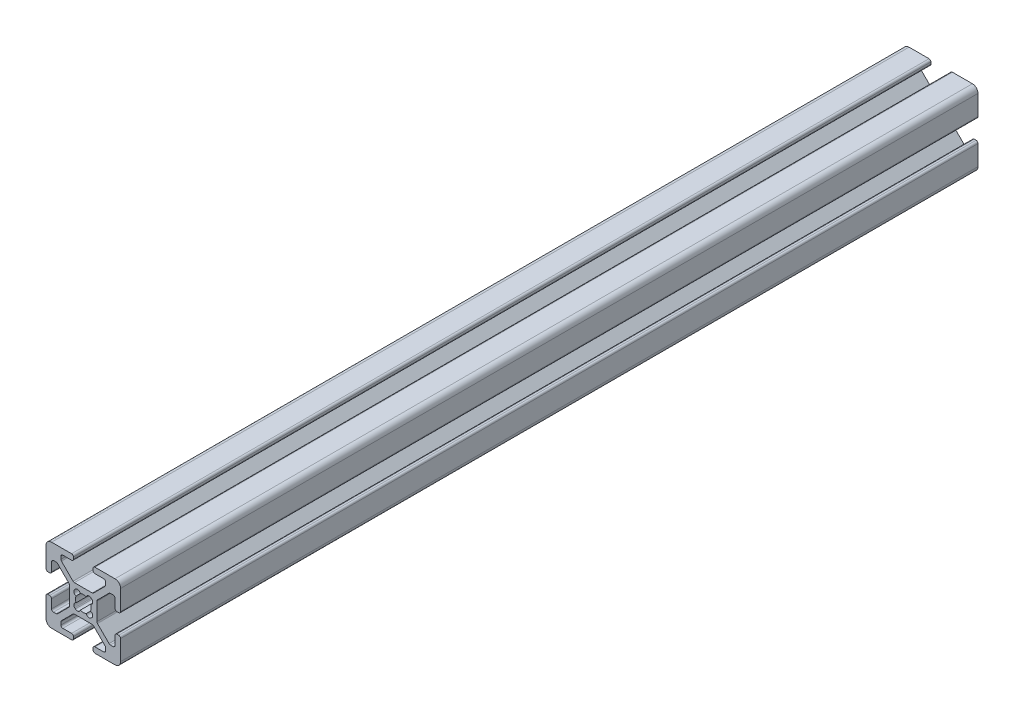
SolidWorks part; units mm, degrees
ref_plane "Front Plane" through (0, 0, 0) normal (0, 0, 1) x (1, 0, 0)
ref_plane "Top Plane" through (0, 0, 0) normal (0, 1, 0) x (1, 0, 0)
ref_plane "Right Plane" through (0, 0, 0) normal (1, 0, 0) x (0, 0, -1)
sketch "Sketch1" plane through (0, 0, 0) normal (0, 0, 1) x (1, 0, 0)
  line B0 (10, 3.138) -> (10, 8.5)
  line B1 (8.5, 10) -> (3.138, 10)
  line B2 (2.63, 9.492) -> (2.63, 9.008)
  line B3 (3.138, 8.5) -> (5.487, 8.5)
  line B4 (5.995, 7.992) -> (5.995, 7.2661)
  line B5 (5.8462, 6.9069) -> (2.7431, 3.8038)
  line B6 (2.3839, 3.655) -> (-2.3839, 3.655)
  line B7 (-2.7431, 3.8038) -> (-5.8462, 6.9069)
  line B8 (-5.995, 7.2661) -> (-5.995, 7.992)
  line B9 (-5.487, 8.5) -> (-3.138, 8.5)
  line B10 (-2.63, 9.008) -> (-2.63, 9.492)
  line B11 (-3.138, 10) -> (-8.5, 10)
  line B12 (-10, 8.5) -> (-10, 3.138)
  line B13 (-9.492, 2.63) -> (-9.008, 2.63)
  line B14 (-8.5, 3.138) -> (-8.5, 5.487)
  line B15 (-7.992, 5.995) -> (-7.2661, 5.995)
  line B16 (-6.9069, 5.8462) -> (-3.8038, 2.7431)
  line B17 (-3.655, 2.3839) -> (-3.655, -2.3839)
  line B18 (-3.8038, -2.7431) -> (-6.9069, -5.8462)
  line B19 (-7.2661, -5.995) -> (-7.992, -5.995)
  line B20 (-8.5, -5.487) -> (-8.5, -3.138)
  line B21 (-9.008, -2.63) -> (-9.492, -2.63)
  line B22 (-10, -3.138) -> (-10, -8.5)
  line B23 (-8.5, -10) -> (-3.138, -10)
  line B24 (-2.63, -9.492) -> (-2.63, -9.008)
  line B25 (-3.138, -8.5) -> (-5.487, -8.5)
  line B26 (-5.995, -7.992) -> (-5.995, -7.2661)
  line B27 (-5.8462, -6.9069) -> (-2.7431, -3.8038)
  line B28 (-2.3839, -3.655) -> (2.3839, -3.655)
  line B29 (2.7431, -3.8038) -> (5.8462, -6.9069)
  line B30 (5.995, -7.2661) -> (5.995, -7.992)
  line B31 (5.487, -8.5) -> (3.138, -8.5)
  line B32 (2.63, -9.008) -> (2.63, -9.492)
  line B33 (3.138, -10) -> (8.5, -10)
  line B34 (10, -8.5) -> (10, -3.138)
  line B35 (9.492, -2.63) -> (9.008, -2.63)
  line B36 (8.5, -3.138) -> (8.5, -5.487)
  line B37 (7.992, -5.995) -> (7.2661, -5.995)
  line B38 (6.9069, -5.8462) -> (3.8038, -2.7431)
  line B39 (3.655, -2.3839) -> (3.655, 2.3839)
  line B40 (3.8038, 2.7431) -> (6.9069, 5.8462)
  line B41 (7.2661, 5.995) -> (7.992, 5.995)
  line B42 (8.5, 5.487) -> (8.5, 3.138)
  line B43 (9.008, 2.63) -> (9.492, 2.63)
  line B44 (-2.1249, -2.3045) -> (-2.3045, -2.1249)
  line B45 (-2.3045, 2.1249) -> (-2.1249, 2.3045)
  line B46 (2.1249, 2.3045) -> (2.3045, 2.1249)
  line B47 (2.3045, -2.1249) -> (2.1249, -2.3045)
  arc B48 (9.492, 2.63) -> (10, 3.138) centre (9.492, 3.138) ccw
  arc B49 (10, 8.5) -> (8.5, 10) centre (8.5, 8.5) ccw
  arc B50 (3.138, 10) -> (2.63, 9.492) centre (3.138, 9.492) ccw
  arc B51 (2.63, 9.008) -> (3.138, 8.5) centre (3.138, 9.008) ccw
  arc B52 (5.487, 8.5) -> (5.995, 7.992) centre (5.487, 7.992) cw
  arc B53 (5.995, 7.2661) -> (5.8462, 6.9069) centre (5.487, 7.2661) cw
  arc B54 (2.7431, 3.8038) -> (2.3839, 3.655) centre (2.3839, 4.163) cw
  arc B55 (-2.3839, 3.655) -> (-2.7431, 3.8038) centre (-2.3839, 4.163) cw
  arc B56 (-5.8462, 6.9069) -> (-5.995, 7.2661) centre (-5.487, 7.2661) cw
  arc B57 (-5.995, 7.992) -> (-5.487, 8.5) centre (-5.487, 7.992) cw
  arc B58 (-3.138, 8.5) -> (-2.63, 9.008) centre (-3.138, 9.008) ccw
  arc B59 (-2.63, 9.492) -> (-3.138, 10) centre (-3.138, 9.492) ccw
  arc B60 (-8.5, 10) -> (-10, 8.5) centre (-8.5, 8.5) ccw
  arc B61 (-10, 3.138) -> (-9.492, 2.63) centre (-9.492, 3.138) ccw
  arc B62 (-9.008, 2.63) -> (-8.5, 3.138) centre (-9.008, 3.138) ccw
  arc B63 (-8.5, 5.487) -> (-7.992, 5.995) centre (-7.992, 5.487) cw
  arc B64 (-7.2661, 5.995) -> (-6.9069, 5.8462) centre (-7.2661, 5.487) cw
  arc B65 (-3.8038, 2.7431) -> (-3.655, 2.3839) centre (-4.163, 2.3839) cw
  arc B66 (-3.655, -2.3839) -> (-3.8038, -2.7431) centre (-4.163, -2.3839) cw
  arc B67 (-6.9069, -5.8462) -> (-7.2661, -5.995) centre (-7.2661, -5.487) cw
  arc B68 (-7.992, -5.995) -> (-8.5, -5.487) centre (-7.992, -5.487) cw
  arc B69 (-8.5, -3.138) -> (-9.008, -2.63) centre (-9.008, -3.138) ccw
  arc B70 (-9.492, -2.63) -> (-10, -3.138) centre (-9.492, -3.138) ccw
  arc B71 (-10, -8.5) -> (-8.5, -10) centre (-8.5, -8.5) ccw
  arc B72 (-3.138, -10) -> (-2.63, -9.492) centre (-3.138, -9.492) ccw
  arc B73 (-2.63, -9.008) -> (-3.138, -8.5) centre (-3.138, -9.008) ccw
  arc B74 (-5.487, -8.5) -> (-5.995, -7.992) centre (-5.487, -7.992) cw
  arc B75 (-5.995, -7.2661) -> (-5.8462, -6.9069) centre (-5.487, -7.2661) cw
  arc B76 (-2.7431, -3.8038) -> (-2.3839, -3.655) centre (-2.3839, -4.163) cw
  arc B77 (2.3839, -3.655) -> (2.7431, -3.8038) centre (2.3839, -4.163) cw
  arc B78 (5.8462, -6.9069) -> (5.995, -7.2661) centre (5.487, -7.2661) cw
  arc B79 (5.995, -7.992) -> (5.487, -8.5) centre (5.487, -7.992) cw
  arc B80 (3.138, -8.5) -> (2.63, -9.008) centre (3.138, -9.008) ccw
  arc B81 (2.63, -9.492) -> (3.138, -10) centre (3.138, -9.492) ccw
  arc B82 (8.5, -10) -> (10, -8.5) centre (8.5, -8.5) ccw
  arc B83 (10, -3.138) -> (9.492, -2.63) centre (9.492, -3.138) ccw
  arc B84 (9.008, -2.63) -> (8.5, -3.138) centre (9.008, -3.138) ccw
  arc B85 (8.5, -5.487) -> (7.992, -5.995) centre (7.992, -5.487) cw
  arc B86 (7.2661, -5.995) -> (6.9069, -5.8462) centre (7.2661, -5.487) cw
  arc B87 (3.8038, -2.7431) -> (3.655, -2.3839) centre (4.163, -2.3839) cw
  arc B88 (3.655, 2.3839) -> (3.8038, 2.7431) centre (4.163, 2.3839) cw
  arc B89 (6.9069, 5.8462) -> (7.2661, 5.995) centre (7.2661, 5.487) cw
  arc B90 (7.992, 5.995) -> (8.5, 5.487) centre (7.992, 5.487) cw
  arc B91 (8.5, 3.138) -> (9.008, 2.63) centre (9.008, 3.138) ccw
  arc B92 (0.804, -1.9351) -> (-0.804, -1.9351) centre (0, 0) cw
  arc B93 (-0.804, -1.9351) -> (-2.1249, -2.3045) centre (-1.5684, -1.748) cw
  arc B94 (-2.3045, -2.1249) -> (-1.9351, -0.804) centre (-1.748, -1.5684) cw
  arc B95 (-1.9351, -0.804) -> (-1.9351, 0.804) centre (0, 0) cw
  arc B96 (-1.9351, 0.804) -> (-2.3045, 2.1249) centre (-1.748, 1.5684) cw
  arc B97 (-2.1249, 2.3045) -> (-0.804, 1.9351) centre (-1.5684, 1.748) cw
  arc B98 (-0.804, 1.9351) -> (0.804, 1.9351) centre (0, 0) cw
  arc B99 (0.804, 1.9351) -> (2.1249, 2.3045) centre (1.5684, 1.748) cw
  arc B100 (2.3045, 2.1249) -> (1.9351, 0.804) centre (1.748, 1.5684) cw
  arc B101 (1.9351, 0.804) -> (1.9351, -0.804) centre (0, 0) cw
  arc B102 (1.9351, -0.804) -> (2.3045, -2.1249) centre (1.748, -1.5684) cw
  arc B103 (2.1249, -2.3045) -> (0.804, -1.9351) centre (1.5684, -1.748) cw
sketch_block_instance "Block1-1"
sketch_block "Block1"
extrude "Boss-Extrude1" add sketch "Sketch1" against normal mid plane 230
ref_axis "Axis1" [suppressed] through (0, 0, 60.5) along (0, 0, -1)
